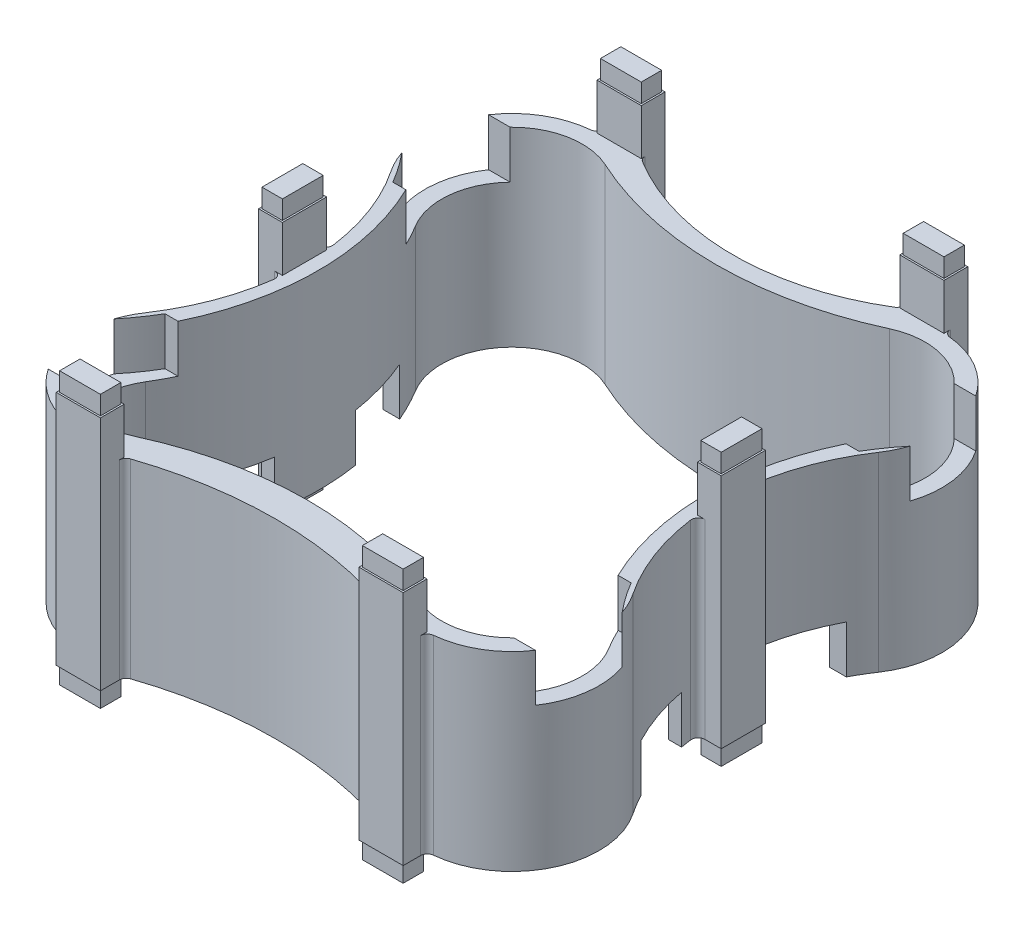
SolidWorks part; units mm, degrees
material "PA 类型 6"
ref_plane "前视基准面" through (0, 0, 0) normal (0, 0, 1) x (1, 0, 0)
ref_plane "上视基准面" through (0, 0, 0) normal (0, 1, 0) x (1, 0, 0)
ref_plane "右视基准面" through (0, 0, 0) normal (1, 0, 0) x (0, 0, -1)
sketch "参考面" plane through (0, 0, 0) normal (0, 1, 0) x (1, 0, 0)
  line L9 (-126.3139, 0) -> (116.7252, 0) construction
  line L10 (121.4406, 121.4406) -> (-121.4406, -121.4406) construction
  line L19 (-81.1154, 0) -> (102.0168, 0) construction
  line L20 (-108.2303, 108.2303) -> (124.7404, -124.7404) construction
  line L37 (0, 0) -> (86.2111, -62.636) construction
  line L56 (0, 63.4476) -> (0, -83.7805) construction
  line L92 (67.1165, -56.1685) -> (56.6027, -48.5298)
  line L94 (74.1596, -46.4745) -> (63.6458, -38.8359)
  line L111 (14.4084, 23.7665) -> (0, 9.3581)
  line L112 (21.4, 67.209) -> (28.6, 67.209)
  line L121 (4.0949, -56.1675) -> (4.0949, -53.2193)
  line L122 (-3.5956, -56.6668) -> (3.5956, -56.6668)
  line L123 (3.5956, -40.6902) -> (-3.5938, -40.6902)
  line L124 (4.0949, -41.1895) -> (4.0949, -44.1377)
  line L125 (-4.0949, -56.1675) -> (-4.0949, -53.2179)
  line L126 (-4.0949, -44.1363) -> (-4.0949, -41.1876)
  line L127 (-4.5418, -52.8684) -> (-4.4444, -52.8684)
  line L128 (-8.5359, -48.8743) -> (-8.5359, -48.4799)
  line L129 (8.5359, -48.8757) -> (8.5359, -48.4813)
  line L130 (4.4444, -52.8698) -> (4.5418, -52.8698)
  line L131 (4.5418, -44.4872) -> (4.4444, -44.4872)
  line L132 (-4.5418, -44.4858) -> (-4.4444, -44.4858)
  line L180 (-67.1165, 56.1685) -> (-56.6027, 48.5298)
  line L181 (-74.1596, 46.4745) -> (-63.6458, 38.8359)
  line L182 (-74.1596, -46.4745) -> (-63.6458, -38.8359)
  line L183 (-67.1165, -56.1685) -> (-56.6027, -48.5298)
  line L194 (-18.9731, -62.4083) -> (18.9712, -62.4083) construction
  line L200 (-11.2634, 52.145) -> (-6.2707, 52.145) construction
  line L201 (-11.2634, 50.8469) -> (-6.2707, 50.8469)
  line L202 (-11.2634, 53.4431) -> (-6.2707, 53.4431)
  line L206 (5.7117, 52.145) -> (0.719, 52.145) construction
  line L207 (5.7117, 53.4431) -> (0.719, 53.4431)
  line L208 (5.7117, 50.8469) -> (0.719, 50.8469)
  line L209 (74.1596, 46.4745) -> (63.6458, 38.8359)
  line L210 (43.9796, 31.9531) -> (60.1362, 43.6915) construction
  line L211 (67.1165, 56.1685) -> (56.6027, 48.5298)
  line L213 (-23.7665, 14.4084) -> (-9.3581, 0)
  line L214 (-58.8004, 0) -> (57.5251, 0) construction
  line L215 (-23.7665, -14.4084) -> (-9.3581, 0)
  line L241 (20.9, 49.291) -> (20.9, 66.709)
  line L242 (21.4, 48.791) -> (28.6, 48.791)
  line L243 (-14.4084, 23.7665) -> (0, 9.3581)
  line L244 (20.9, 58) -> (35.2287, 58) construction
  line L245 (25, 67.209) -> (25, 48.791) construction
  line L246 (29.1, 66.709) -> (29.1, 49.291)
  line L247 (23.7665, -14.4084) -> (9.3581, 0)
  line L248 (23.7665, 14.4084) -> (9.3581, 0)
  line L249 (-14.4084, -23.7665) -> (0, -9.3581)
  line L250 (14.4084, -23.7665) -> (0, -9.3581)
  line L255 (25.5, -41.5) -> (19, -41.5)
  line L256 (-25.5, 41.5) -> (-19, 41.5)
  line L257 (-25.5, 41.5) -> (-25.5, 38)
  line L258 (-25.5, 38) -> (-19, 38)
  line L259 (-19, 41.5) -> (-19, 38)
  line L260 (-34, 3.25) -> (-30.5, 3.25)
  line L261 (-34, 3.25) -> (-34, -3.25)
  line L262 (-34, -3.25) -> (-30.5, -3.25)
  line L263 (-30.5, 3.25) -> (-30.5, -3.25)
  line L264 (-25.5, -38) -> (-19, -38)
  line L265 (-25.5, -38) -> (-25.5, -41.5)
  line L266 (-25.5, -41.5) -> (-19, -41.5)
  line L267 (-19, -38) -> (-19, -41.5)
  line L268 (19, -38) -> (19, -41.5)
  line L269 (25.5, -38) -> (19, -38)
  line L270 (25.5, -38) -> (25.5, -41.5)
  line L271 (34, -3.25) -> (30.5, -3.25)
  line L272 (30.5, 3.25) -> (30.5, -3.25)
  line L273 (34, 3.25) -> (30.5, 3.25)
  line L274 (34, 3.25) -> (34, -3.25)
  line L275 (25.5, 38) -> (19, 38)
  line L276 (19, 41.5) -> (19, 38)
  line L277 (25.5, 41.5) -> (25.5, 38)
  line L278 (25.5, 41.5) -> (19, 41.5)
  circle A40 centre (9.9853, 9.9853) radius 1.0734
  circle A65 centre (12.7313, 12.7313) radius 1.0734
  circle A66 centre (15.2276, 15.2276) radius 1.5477
  circle A67 centre (-15.2276, 15.2276) radius 1.5477
  circle A68 centre (-12.7313, 12.7313) radius 1.0734
  circle A69 centre (-9.9853, 9.9853) radius 1.0734
  circle A70 centre (-9.9853, -9.9853) radius 1.0734
  circle A71 centre (-12.7313, -12.7313) radius 1.0734
  circle A72 centre (-15.2276, -15.2276) radius 1.5477
  circle A82 centre (15.2276, -15.2276) radius 1.5477
  circle A83 centre (12.7313, -12.7313) radius 1.0734
  circle A84 centre (9.9853, -9.9853) radius 1.0734
  circle A85 centre (27.9589, -27.9589) radius 3.1454
  circle A86 centre (-27.9589, -27.9589) radius 3.1454
  circle A101 centre (-27.9589, 27.9589) radius 3.1454
  circle A102 centre (27.9589, 27.9589) radius 3.1454
  circle A104 centre (43.9796, -31.9531) radius 1.5477
  circle A105 centre (60.1362, -43.6915) radius 1.5477
  circle A106 centre (-60.1362, -43.6915) radius 1.5477
  circle A113 centre (-23.2458, 52.145) radius 1.2981
  circle A114 centre (-43.9796, -31.9531) radius 1.5477
  circle A115 centre (60.1362, 43.6915) radius 1.5477
  circle A116 centre (43.9796, 31.9531) radius 1.5477
  circle A117 centre (-43.9796, 31.9531) radius 1.5477
  circle A118 centre (-60.1362, 43.6915) radius 1.5477
  arc A120 (67.1165, -56.1685) -> (74.1596, -46.4745) centre (70.638, -51.3215) ccw
  arc A121 (27.2174, -63.5024) -> (56.6027, -48.5298) centre (45.7245, -63.5024) cw
  arc A128 (-4.0949, -56.1675) -> (-3.5956, -56.6668) centre (-4.0949, -56.6668) ccw
  arc A129 (4.0949, -56.1675) -> (3.5956, -56.6668) centre (4.0949, -56.6668) cw
  arc A130 (4.0949, -41.1895) -> (3.5956, -40.6902) centre (4.0949, -40.6902) ccw
  arc A131 (-4.0949, -41.1876) -> (-3.5938, -40.6902) centre (-4.0931, -40.6884) cw
  arc A132 (8.5359, -48.4813) -> (4.5418, -44.4872) centre (4.5418, -48.4813) ccw
  arc A133 (-4.5418, -44.4858) -> (-8.5359, -48.4799) centre (-4.5418, -48.4799) ccw
  arc A134 (-4.5418, -52.8684) -> (-8.5359, -48.8743) centre (-4.5418, -48.8743) cw
  arc A135 (8.5359, -48.8757) -> (4.5418, -52.8698) centre (4.5418, -48.8757) cw
  arc A136 (4.0949, -44.1377) -> (4.4444, -44.4872) centre (4.4444, -44.1377) ccw
  arc A137 (4.0949, -53.2193) -> (4.4444, -52.8698) centre (4.4444, -53.2193) cw
  arc A138 (-4.0949, -44.1363) -> (-4.4444, -44.4858) centre (-4.4444, -44.1363) cw
  arc A139 (-4.0949, -53.2179) -> (-4.4444, -52.8684) centre (-4.4444, -53.2179) ccw
  arc A165 (-11.2634, 50.8469) -> (-11.2634, 53.4431) centre (-11.2634, 52.145) cw
  arc A166 (-6.2707, 53.4431) -> (-6.2707, 50.8469) centre (-6.2707, 52.145) cw
  arc A169 (5.7117, 53.4431) -> (5.7117, 50.8469) centre (5.7117, 52.145) cw
  arc A170 (0.719, 50.8469) -> (0.719, 53.4431) centre (0.719, 52.145) cw
  circle A175 centre (0, -38.4435) radius 1.5477
  circle A176 centre (0, -58.9135) radius 1.5477
  arc A177 (67.1165, 56.1685) -> (74.1596, 46.4745) centre (70.638, 51.3215) cw
  arc A178 (63.6458, 38.8359) -> (63.6458, -38.8359) centre (91.8617, 0) ccw
  circle A179 centre (43.9796, -31.9531) radius 5.9912 construction
  arc A180 (35.3497, 58.9683) -> (56.6027, 48.5298) centre (48.7329, 59.3617) ccw
  arc A181 (-67.1165, 56.1685) -> (-74.1596, 46.4745) centre (-70.638, 51.3215) ccw
  arc A182 (-35.3497, 58.9683) -> (-56.6027, 48.5298) centre (-48.7329, 59.3617) cw
  arc A183 (-63.6458, 38.8359) -> (-63.6458, -38.8359) centre (-91.8617, 0) cw
  arc A184 (-67.1165, -56.1685) -> (-74.1596, -46.4745) centre (-70.638, -51.3215) cw
  arc A185 (-27.2174, -63.5024) -> (-56.6027, -48.5298) centre (-45.7245, -63.5024) ccw
  arc A190 (-23.7665, 14.4084) -> (-29.7764, 19.3723) centre (-52.8107, -14.6358) ccw
  arc A191 (-23.7665, -14.4084) -> (-29.7764, -19.3723) centre (-52.8107, 14.6358) cw
  arc A192 (-29.7764, -19.3723) -> (-29.7764, 19.3723) centre (-91.8617, 0) ccw
  circle A202 centre (25, 69.659) radius 1.05
  arc A203 (20.9, 66.709) -> (21.4, 67.209) centre (20.9, 67.209) cw
  arc A204 (20.9, 49.291) -> (21.4, 48.791) centre (20.9, 48.791) ccw
  circle A205 centre (25, 46.341) radius 1.05
  arc A206 (29.1, 66.709) -> (28.6, 67.209) centre (29.1, 67.209) ccw
  arc A207 (29.1, 49.291) -> (28.6, 48.791) centre (29.1, 48.791) cw
  arc A208 (-14.4084, 23.7665) -> (-19.3723, 29.7764) centre (14.6358, 52.8107) cw
  arc A209 (-19.3723, 29.7764) -> (19.3723, 29.7764) centre (0, 91.8617) ccw
  arc A210 (14.4084, 23.7665) -> (19.3723, 29.7764) centre (-14.6358, 52.8107) ccw
  arc A211 (23.7665, 14.4084) -> (29.7764, 19.3723) centre (52.8107, -14.6358) cw
  arc A212 (29.7764, 19.3723) -> (29.7764, -19.3723) centre (91.8617, 0) ccw
  arc A213 (23.7665, -14.4084) -> (29.7764, -19.3723) centre (52.8107, 14.6358) ccw
  arc A214 (14.4084, -23.7665) -> (19.3723, -29.7764) centre (-14.6358, -52.8107) cw
  arc A215 (19.3723, -29.7764) -> (-19.3723, -29.7764) centre (0, -91.8617) ccw
  arc A216 (-14.4084, -23.7665) -> (-19.3723, -29.7764) centre (14.6358, -52.8107) ccw
  point P77 (0, 0)
  point P112 (-8.7671, 52.145)
  point P168 (3.2153, 52.145)
  point P443 (0, 0)
  dimension "D1" = 4
  dimension "D3" = 58
  dimension "D5" = 8.2
  dimension "D2" = 0.5
  dimension "D4" = 2.45
  dimension "D6" = 7.2
  dimension "D7" = 25
  dimension "D8" = 19
  dimension "D9" = 30.5
  dimension "D14" = 6.5
  dimension "D15" = 3.5
  dimension "D16" = 38
  dimension "D17" = 38
sketch "草图2" plane through (0, 0, 0) normal (0, 1, 0) x (1, 0, 0)
  line L1 (-61.3007, 0) -> (77.257, 0) construction
  line L8 (-30.5, 3.25) -> (-34, 3.25)
  line L9 (-34, 3.25) -> (-34, -3.25)
  line L31 (-34, -3.25) -> (-30.5, -3.25)
  line L33 (-25.5, 38) -> (-25.5, 41.5)
  line L56 (-25.5, 41.5) -> (-19, 41.5)
  line L57 (-19, 41.5) -> (-19, 38)
  line L58 (-25.5, -38) -> (-25.5, -41.5)
  line L59 (-25.5, -41.5) -> (-19, -41.5)
  line L60 (-19, -41.5) -> (-19, -38)
  line L61 (19, -41.5) -> (19, -38)
  line L62 (25.5, -41.5) -> (19, -41.5)
  line L63 (25.5, -38) -> (25.5, -41.5)
  line L64 (19, 41.5) -> (19, 38)
  line L65 (25.5, 41.5) -> (19, 41.5)
  line L66 (25.5, 38) -> (25.5, 41.5)
  line L67 (34, -3.25) -> (30.5, -3.25)
  line L68 (34, 3.25) -> (34, -3.25)
  line L69 (30.5, 3.25) -> (34, 3.25)
  line L74 (-126.3139, 0) -> (116.7252, 0) construction
  line L75 (0, 68.5797) -> (0, -68.5797) construction
  line L76 (0, 63.4476) -> (0, -83.7805) construction
  line L77 (-108.2303, 108.2303) -> (124.7404, -124.7404) construction
  arc A49 (-25.5, 38) -> (-35.8347, 18.0724) centre (-25.2016, 25.2016) ccw
  arc A52 (-20.8758, 34.5817) -> (-34.0392, 19.854) centre (-25.2016, 25.2016) ccw
  arc A53 (-34.0392, -19.854) -> (-34.0392, 19.854) centre (-66.8509, 0) ccw
  arc A55 (-35.8347, -18.0724) -> (-30.5, -3.25) centre (-62.7894, 0) ccw
  arc A56 (-25.5, -38) -> (-35.8347, -18.0724) centre (-25.2016, -25.2016) cw
  arc A57 (-20.8758, -34.5817) -> (-34.0392, -19.854) centre (-25.2016, -25.2016) cw
  arc A59 (-30.5, 3.25) -> (-35.8347, 18.0724) centre (-62.7894, 0) ccw
  arc A62 (30.5, 3.25) -> (35.8347, 18.0724) centre (62.7894, 0) cw
  arc A65 (20.8758, -34.5817) -> (34.0392, -19.854) centre (25.2016, -25.2016) ccw
  arc A66 (25.5, -38) -> (35.8347, -18.0724) centre (25.2016, -25.2016) ccw
  arc A69 (35.8347, -18.0724) -> (30.5, -3.25) centre (62.7894, 0) cw
  arc A70 (34.0392, -19.854) -> (34.0392, 19.854) centre (66.8509, 0) cw
  arc A71 (20.8758, 34.5817) -> (34.0392, 19.854) centre (25.2016, 25.2016) cw
  arc A72 (25.5, 38) -> (35.8347, 18.0724) centre (25.2016, 25.2016) cw
  arc A73 (-19, 38) -> (19, 38) centre (0, 67.9818) ccw
  arc A74 (-20.8758, 34.5817) -> (20.8758, 34.5817) centre (0, 79.8492) ccw
  arc A75 (-19, -38) -> (19, -38) centre (0, -91.6977) cw
  arc A76 (-20.8758, -34.5817) -> (20.8758, -34.5817) centre (0, -79.8492) cw
  point P33 (-28.5, 0)
  point P34 (28.5, 0)
  point P37 (0, 30)
  point P38 (0, -30)
  point P44 (-36.5661, 31.0954)
  point P54 (0, 32.4866)
  dimension "D1" = 2
  dimension "D3" = 60
  dimension "D5" = 2.4866
  dimension "D2" = 57
  dimension "D4" = 48
extrude "主结构-28mm-铝柱补偿7mm" add sketch "草图2" against normal blind 28
sketch "草图9" plane through (0, 0, 0) normal (0, 1, 0) x (1, 0, 0)
  line L0 (-25.5, 41.5) -> (-19, 41.5)
  line L1 (-19, 41.5) -> (-19, 38)
  line L2 (-19, 38) -> (-25.5, 38)
  line L3 (-25.5, 38) -> (-25.5, 41.5)
  line L4 (-34, 3.25) -> (-30.5, 3.25)
  line L5 (-30.5, 3.25) -> (-30.5, -3.25)
  line L6 (-30.5, -3.25) -> (-34, -3.25)
  line L7 (-34, -3.25) -> (-34, 3.25)
  line L8 (-25.5, -38) -> (-19, -38)
  line L9 (-19, -38) -> (-19, -41.5)
  line L10 (-19, -41.5) -> (-25.5, -41.5)
  line L11 (-25.5, -41.5) -> (-25.5, -38)
  line L12 (0, 0) -> (0, 49.4307) construction
  line L13 (25.5, -41.5) -> (25.5, -38)
  line L14 (19, -41.5) -> (25.5, -41.5)
  line L15 (19, -38) -> (19, -41.5)
  line L16 (25.5, -38) -> (19, -38)
  line L17 (34, -3.25) -> (34, 3.25)
  line L18 (30.5, -3.25) -> (34, -3.25)
  line L19 (30.5, 3.25) -> (30.5, -3.25)
  line L20 (34, 3.25) -> (30.5, 3.25)
  line L21 (25.5, 38) -> (25.5, 41.5)
  line L22 (19, 38) -> (25.5, 38)
  line L23 (19, 41.5) -> (19, 38)
  line L24 (25.5, 41.5) -> (19, 41.5)
extrude "上板支撑" add sketch "草图9" along normal blind 6.75
sketch "草图5" plane through (0, 0, 0) normal (0, 1, 0) x (1, 0, 0)
  line L0 (-68.648, 0) -> (77.219, 0) construction
  line L1 (-126.3139, 0) -> (116.7252, 0) construction
  line L2 (0, 57.3258) -> (0, -69.9488) construction
  line L3 (0, 63.4476) -> (0, -83.7805) construction
  line L4 (-34, 3.25) -> (-30.5, 3.25) construction
  line L5 (-33.75, 3) -> (-30.75, 3)
  line L6 (-33.75, 3) -> (-33.75, -3)
  line L7 (-33.75, -3) -> (-30.75, -3)
  line L8 (-30.75, 3) -> (-30.75, -3)
  line L9 (-34, 3.25) -> (-34, -3.25) construction
  line L10 (-19, -38) -> (-19, -41.5) construction
  line L11 (-25.25, -38.25) -> (-19.25, -38.25)
  line L12 (-25.25, -38.25) -> (-25.25, -41.25)
  line L13 (-25.25, -41.25) -> (-19.25, -41.25)
  line L14 (-19.25, -38.25) -> (-19.25, -41.25)
  line L15 (-25.5, -41.5) -> (-19, -41.5) construction
  line L16 (-25.25, 41.25) -> (-19.25, 41.25)
  line L17 (-19.25, 38.25) -> (-19.25, 41.25)
  line L18 (-25.25, 38.25) -> (-19.25, 38.25)
  line L19 (-25.25, 38.25) -> (-25.25, 41.25)
  line L20 (25.25, 38.25) -> (25.25, 41.25)
  line L21 (25.25, 38.25) -> (19.25, 38.25)
  line L22 (19.25, 38.25) -> (19.25, 41.25)
  line L23 (25.25, 41.25) -> (19.25, 41.25)
  line L24 (19.25, -38.25) -> (19.25, -41.25)
  line L25 (25.25, -41.25) -> (19.25, -41.25)
  line L26 (25.25, -38.25) -> (25.25, -41.25)
  line L27 (25.25, -38.25) -> (19.25, -38.25)
  line L28 (30.75, 3) -> (30.75, -3)
  line L29 (33.75, -3) -> (30.75, -3)
  line L30 (33.75, 3) -> (33.75, -3)
  line L31 (33.75, 3) -> (30.75, 3)
  dimension "D1" = 0.25
  dimension "D2" = 0.25
  dimension "D3" = 3
  dimension "D4" = 0.25
  dimension "D5" = 0.25
extrude "凸台-拉伸3" add sketch "草图5" along normal blind 2.75 from surface starting at face at (-22.25, 6.75, -39.75)
sketch "草图6" plane through (0, -28, 0) normal (0, -1, 0) x (1, 0, 0)
  line L0 (-44.389, 0) -> (42.3877, 0) construction
  line L1 (0, 51.2716) -> (0, -51.2716) construction
  line L2 (-25.25, 41.25) -> (-19.25, 41.25)
  line L3 (-33.75, 3) -> (-30.75, 3)
  line L4 (-33.75, 3) -> (-33.75, -3)
  line L5 (-33.75, -3) -> (-30.75, -3)
  line L6 (-30.75, 3) -> (-30.75, -3)
  line L7 (-25.25, -38.25) -> (-19.25, -38.25)
  line L8 (-25.25, -38.25) -> (-25.25, -41.25)
  line L9 (-25.25, -41.25) -> (-19.25, -41.25)
  line L10 (-19.25, -38.25) -> (-19.25, -41.25)
  line L11 (-19.25, 38.25) -> (-19.25, 41.25)
  line L12 (-25.25, 38.25) -> (-19.25, 38.25)
  line L13 (-25.25, 38.25) -> (-25.25, 41.25)
  line L14 (25.25, 38.25) -> (25.25, 41.25)
  line L15 (25.25, 38.25) -> (19.25, 38.25)
  line L16 (19.25, 38.25) -> (19.25, 41.25)
  line L17 (19.25, -38.25) -> (19.25, -41.25)
  line L18 (25.25, -41.25) -> (19.25, -41.25)
  line L19 (25.25, -38.25) -> (25.25, -41.25)
  line L20 (25.25, -38.25) -> (19.25, -38.25)
  line L21 (30.75, 3) -> (30.75, -3)
  line L22 (33.75, -3) -> (30.75, -3)
  line L23 (33.75, 3) -> (33.75, -3)
  line L24 (33.75, 3) -> (30.75, 3)
  line L25 (25.25, 41.25) -> (19.25, 41.25)
  line L26 (-34, 3.25) -> (-30.5, 3.25) construction
  line L27 (-34, -3.25) -> (-34, 3.25) construction
  line L28 (-25.5, -41.5) -> (-25.5, -38) construction
  line L29 (-19, -41.5) -> (-25.5, -41.5) construction
  dimension "D1" = 0.25
  dimension "D2" = 0.25
  dimension "D3" = 0.25
  dimension "D4" = 0.25
  dimension "D5" = 3
extrude "凸台-拉伸4" add sketch "草图6" along normal blind 2.5
fillet "圆角1" radius 1 12 edges at (30.5, -14, -3.25) (25.5, -14, -38) (-19, -14, -38) (19, -14, -38) (-25.5, -14, -38) (-30.5, -14, -3.25) (19, -14, 38) (30.5, -14, 3.25) (25.5, -14, 38) (-19, -14, 38) (-25.5, -14, 38) (-30.5, -14, 3.25)
sketch "草图7" plane through (0, 0, 0) normal (0, 1, 0) x (1, 0, 0)
  line L0 (-43.0337, 0) -> (42.851, 0) construction
  line L1 (0, 36.718) -> (0, -44.8375) construction
  line L2 (0, 0) -> (-41.2356, -29.9594) construction
  line L3 (-34.2586, -16.7459) -> (-32.3492, -16.7459)
  line L4 (-35.8097, -32.3679) -> (-32.6409, -32.3679)
  line L5 (34.2586, -16.7459) -> (32.3492, -16.7459)
  line L6 (35.8097, -32.3679) -> (32.6409, -32.3679)
  line L8 (-34.2586, 16.7459) -> (-32.3492, 16.7459)
  line L9 (-35.8097, 32.3679) -> (-32.6409, 32.3679)
  line L10 (35.8097, 32.3679) -> (32.6409, 32.3679)
  line L11 (34.2586, 16.7459) -> (32.3492, 16.7459)
  arc A0 (-34.0392, -19.854) -> (-32.6409, -32.3679) centre (-25.2016, -25.2016) ccw
  arc A1 (-37.3416, -21.1387) -> (-35.8097, -32.3679) centre (-25.2016, -25.2016) ccw
  arc A2 (-37.3416, -21.1387) -> (-34.2586, -16.7459) centre (-62.7894, 0) ccw
  arc A3 (-34.0392, -19.854) -> (-32.3492, -16.7459) centre (-66.8509, 0) ccw
  arc A4 (34.0392, -19.854) -> (32.3492, -16.7459) centre (66.8509, 0) cw
  arc A5 (37.3416, -21.1387) -> (34.2586, -16.7459) centre (62.7894, 0) cw
  arc A6 (37.3416, -21.1387) -> (35.8097, -32.3679) centre (25.2016, -25.2016) cw
  arc A7 (34.0392, -19.854) -> (32.6409, -32.3679) centre (25.2016, -25.2016) cw
  arc A12 (-34.0392, 19.854) -> (-32.3492, 16.7459) centre (-66.8509, 0) cw
  arc A13 (-37.3416, 21.1387) -> (-34.2586, 16.7459) centre (-62.7894, 0) cw
  arc A14 (-37.3416, 21.1387) -> (-35.8097, 32.3679) centre (-25.2016, 25.2016) cw
  arc A15 (-34.0392, -19.854) -> (-34.0392, 19.854) centre (-66.8509, 0) ccw construction
  arc A16 (-34.0392, 19.854) -> (-32.6409, 32.3679) centre (-25.2016, 25.2016) cw
  arc A17 (34.0392, 19.854) -> (32.6409, 32.3679) centre (25.2016, 25.2016) ccw
  arc A18 (37.3416, 21.1387) -> (35.8097, 32.3679) centre (25.2016, 25.2016) ccw
  arc A19 (37.3416, 21.1387) -> (34.2586, 16.7459) centre (62.7894, 0) ccw
  arc A20 (34.0392, 19.854) -> (32.3492, 16.7459) centre (66.8509, 0) ccw
  arc A21 (-20.8758, 34.5817) -> (-34.0392, 19.854) centre (-25.2016, 25.2016) ccw construction
  arc A22 (-34.0392, -19.854) -> (-20.8758, -34.5817) centre (-25.2016, -25.2016) ccw construction
  arc A23 (35.8347, 18.0724) -> (26.4059, 37.9467) centre (25.2016, 25.2016) ccw construction
  arc A24 (-26.4059, 37.9467) -> (-35.8347, 18.0724) centre (-25.2016, 25.2016) ccw construction
  point P50 (0, 0)
  point P51 (0, 0)
  point P55 (0, 0)
  dimension "D1" = 36
extrude "电调过线" cut sketch "草图7" against normal blind 7
sketch "草图8" plane through (0, -28, 0) normal (0, -1, 0) x (1, 0, 0)
  line L0 (-48.2566, 0) -> (46.2095, 0) construction
  line L1 (0, 0) -> (0, -36.4146) construction
  line L2 (-30.8873, -5.9516) -> (-28.9646, -5.9516)
  line L3 (-34.0577, -15.0884) -> (-31.5928, -15.0884)
  line L4 (-34.0577, 15.0884) -> (-31.5928, 15.0884)
  line L5 (-30.8873, 5.9516) -> (-28.9646, 5.9516)
  line L6 (30.8873, -5.9516) -> (28.9646, -5.9516)
  line L7 (34.0577, -15.0884) -> (31.5928, -15.0884)
  line L8 (30.8873, 5.9516) -> (28.9646, 5.9516)
  line L9 (34.0577, 15.0884) -> (31.5928, 15.0884)
  arc A0 (-35.8347, -18.0724) -> (-30.6345, -4.3851) centre (-62.7894, 0) ccw construction
  arc A1 (-34.0392, -19.854) -> (-34.0392, 19.854) centre (-66.8509, 0) ccw construction
  arc A2 (-30.8873, -5.9516) -> (-34.0577, -15.0884) centre (-62.7894, 0) cw
  arc A3 (-28.9646, -5.9516) -> (-31.5928, -15.0884) centre (-66.8509, 0) cw
  arc A4 (-30.8873, 5.9516) -> (-34.0577, 15.0884) centre (-62.7894, 0) ccw
  arc A5 (-28.9646, 5.9516) -> (-31.5928, 15.0884) centre (-66.8509, 0) ccw
  arc A6 (30.8873, -5.9516) -> (34.0577, -15.0884) centre (62.7894, 0) ccw
  arc A7 (28.9646, -5.9516) -> (31.5928, -15.0884) centre (66.8509, 0) ccw
  arc A8 (28.9646, 5.9516) -> (31.5928, 15.0884) centre (66.8509, 0) cw
  arc A9 (30.8873, 5.9516) -> (34.0577, 15.0884) centre (62.7894, 0) cw
extrude "电源过线" cut sketch "草图8" against normal blind 7
